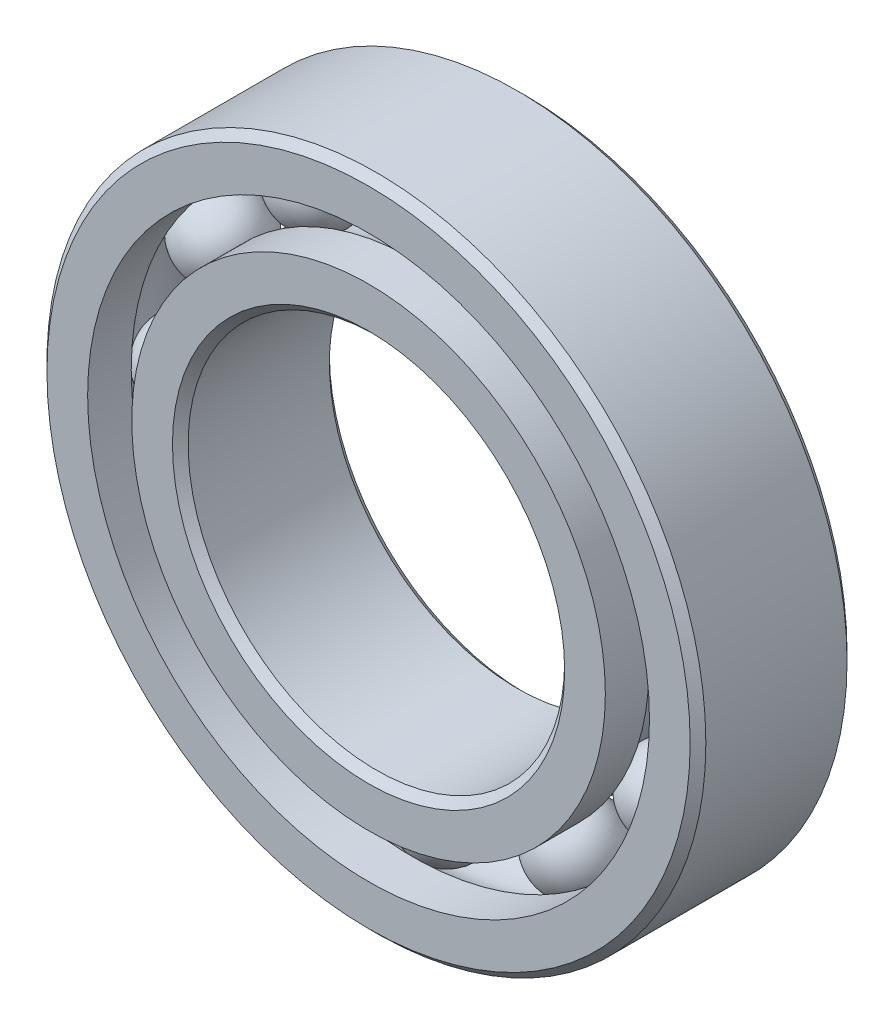
SolidWorks part; units mm, degrees
ref_plane "Front Plane" through (0, 0, 0) normal (0, 0, 1) x (1, 0, 0)
ref_plane "Top Plane" through (0, 0, 0) normal (0, 1, 0) x (1, 0, 0)
ref_plane "Right Plane" through (0, 0, 0) normal (1, 0, 0) x (0, 0, -1)
sketch "Sketch1" plane through (0, 0, 0) normal (1, 0, 0) x (0, 0, -1)
  line L0 (-2.5, 0) -> (2.5, 0) construction
  line L1 (0, 10.5) -> (0, -10.5) construction
  line L2 (2.25, 10.5) -> (-2.25, 10.5)
  line L3 (-2.25, 10.5) -> (-2.5, 10.25)
  line L4 (-2.5, 10.25) -> (-2.5, 8.9533)
  line L5 (-2.5, 8.9533) -> (-1.1111, 8.9533)
  line L6 (2.5, 8.9533) -> (1.1111, 8.9533)
  line L7 (2.5, 10.25) -> (2.5, 8.9533)
  line L8 (2.25, 10.5) -> (2.5, 10.25)
  line L9 (0, 10.5) -> (0, 8.25) construction
  line L10 (0, 8.25) -> (0, 6) construction
  arc A0 (-1.1111, 8.9533) -> (1.1111, 8.9533) centre (0, 8.25) cw
  point P14 (0, 6)
  dimension "Width" = 5
  dimension "OD" = 21
  dimension "D1" = 45
  dimension "D2" = 0.25
  dimension "Shaft Dia" = 12
  dimension "D3" = 2.2222
  dimension "D4" = 0.7033
revolve "Revolve1" add sketch "Sketch1" angle 360 about L0
sketch "Sketch3" plane through (0, 0, 0) normal (1, 0, 0) x (0, 0, -1)
  line L0 (-2.5, 7.5467) -> (-1.1111, 7.5467)
  line L1 (0, 10.5) -> (0, -10.5) construction
  line L2 (-2.5, 10.25) -> (-2.5, 8.9533) construction
  line L3 (-2.5, 7.5467) -> (-2.5, 6.25)
  line L4 (-2.25, 10.5) -> (-2.5, 10.25) construction
  line L5 (-2.5, 6.25) -> (-2.25, 6)
  line L6 (-2.25, 6) -> (2.25, 6)
  line L7 (2.25, 10.5) -> (2.25, -10.5) construction
  line L8 (2.25, 6) -> (2.5, 6.25)
  line L9 (2.5, -10.25) -> (2.5, 10.25) construction
  line L10 (2.5, 6.25) -> (2.5, 7.5467)
  line L11 (2.5, 7.5467) -> (1.1111, 7.5467)
  line L13 (2.25, 10.5) -> (2.5, 10.25) construction
  arc A0 (1.1111, 8.9533) -> (-1.1111, 8.9533) centre (0, 8.25) ccw construction
  arc A1 (1.1111, 7.5467) -> (-1.1111, 7.5467) centre (0, 8.25) cw
revolve "Revolve3" add sketch "Sketch3" angle 360 about L0
sketch "Sketch4" plane through (0, 0, 0) normal (1, 0, 0) x (0, 0, -1)
  line L0 (-1.315, 8.25) -> (1.315, 8.25)
  arc A2 (-1.315, 8.25) -> (1.315, 8.25) centre (0, 8.25) cw
  arc A3 (1.1111, 8.9533) -> (-1.1111, 8.9533) centre (0, 8.25) ccw construction
revolve "Revolve4" add sketch "Sketch4" angle 360 about L0
ref_axis "Axis1" through (0, 0, -2.5) along (0, 0, 1)
pattern_circular "CirPattern1" count 12 every 30 about axis through (0, 0, -2.5) along (0, 0, 1) of bodies 104
sketch "Sketch5" plane through (0, 0, 0) normal (1, 0, 0) x (0, 0, -1)
  line L0 (-2.5, 8.9533) -> (-1.1111, 8.9533) construction
  line L1 (-2.375, 8.9533) -> (-1.315, 8.9533)
  line L2 (-2.375, 8.9533) -> (-2.375, 7.5467)
  line L3 (-2.375, 7.5467) -> (-1.315, 7.5467)
  line L4 (-1.315, 8.9533) -> (-1.315, 7.5467)
  line L5 (-2.5, 7.5467) -> (-1.1111, 7.5467) construction
  line L6 (2.5, 8.9533) -> (1.1111, 8.9533) construction
  line L7 (2.375, 8.9533) -> (1.315, 8.9533)
  line L8 (2.375, 8.9533) -> (2.375, 7.5467)
  line L9 (2.375, 7.5467) -> (1.315, 7.5467)
  line L10 (1.315, 8.9533) -> (1.315, 7.5467)
  line L11 (2.5, 7.5467) -> (1.1111, 7.5467) construction
  line L12 (-2.25, 10.5) -> (-2.5, 10.25) construction
  point P18 (-2.375, 10.375)
equation "\"D2@Sketch1\" = \"Width@Sketch1\"*.05"
equation "\"D3@Sketch1\" = \"Width@Sketch1\"/2.25"
equation "\"D4@Sketch1\" = (((\"OD@Sketch1\"-\"Width@Sketch1\")/2)/3.25)/3.5"
equation "\"D2@CirPattern1\" = 360/\"Balls@CirPattern1\""
